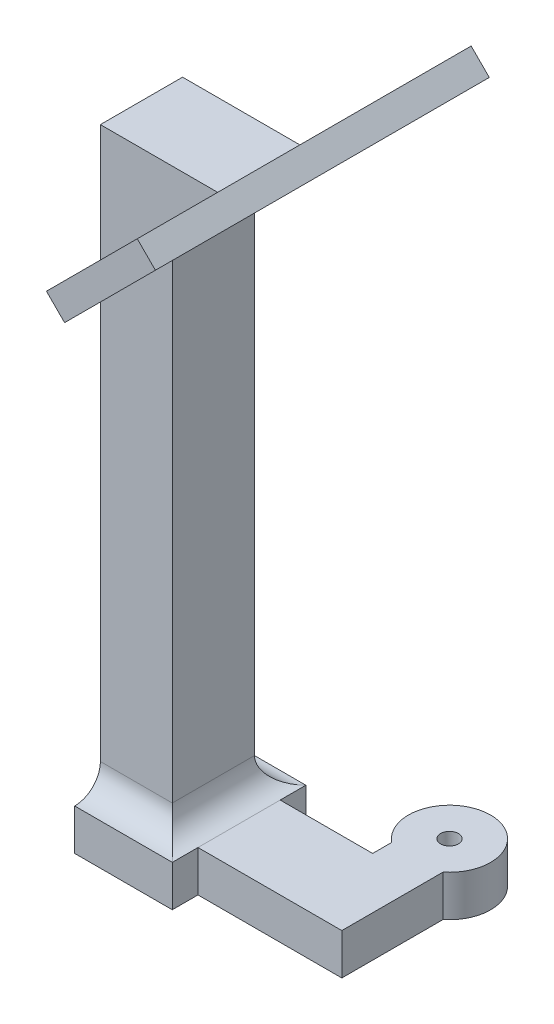
SolidWorks part; units mm, degrees
ref_plane "Front Plane" through (0, 0, 0) normal (0, 0, 1) x (1, 0, 0)
ref_plane "Top Plane" through (0, 0, 0) normal (0, 1, 0) x (1, 0, 0)
ref_plane "Right Plane" through (0, 0, 0) normal (1, 0, 0) x (0, 0, -1)
sketch "Sketch1" plane through (0, 0, 0) normal (1, 0, 0) x (0, 0, -1)
  line L0 (0, 15) -> (80, 15) construction
  line L1 (0, 0) -> (80, 0)
  line L2 (0, 0) -> (0, 30)
  line L3 (0, 30) -> (80, 30)
  line L4 (80, 0) -> (80, 30)
  line L5 (40, 15) -> (40, 30) construction
  circle A0 centre (17.5, 15) radius 1.75
  circle A1 centre (62.5, 15) radius 1.75
  dimension "D3" = 3.5
  dimension "D1" = 80
  dimension "D2" = 30
  dimension "D4" = 45
  dimension "D5" = 22.5
sketch "Sketch3" plane through (0, 0, 0) normal (0, 0, 1) x (1, 0, 0)
  line L0 (-3.5355, 33.5355) -> (0, 30)
  line L1 (0, 30) -> (17.6777, 47.6777)
  line L2 (17.6777, 47.6777) -> (14.1421, 51.2132)
  line L3 (14.1421, 51.2132) -> (-3.5355, 33.5355)
  line L4 (21.6115, 0) -> (-21.6115, 0) construction
  line L5 (0, 15) -> (0, 30) construction
  dimension "D1" = 5
  dimension "D2" = 45
  dimension "D3" = 25
  dimension "D4" = 30
  dimension "D5" = 0
extrude "Boss-Extrude2" add sketch "Sketch3" against normal blind 65
sketch "Sketch4" plane through (-18.5355, 18.5355, 0) normal (-0.7071, 0.7071, 0) x (0, 0, 1)
  line L0 (-65, 33.7132) -> (0, 33.7132) construction
  line L1 (-65, 46.2132) -> (-65, 21.2132) construction
  line L2 (0, 46.2132) -> (0, 21.2132) construction
  line L3 (-32.5, 46.2132) -> (-32.5, 21.2132) construction
  line L4 (-65, 46.2132) -> (0, 46.2132) construction
  line L5 (-65, 21.2132) -> (0, 21.2132) construction
  circle A0 centre (-10, 33.7132) radius 1.75
  circle A1 centre (-55, 33.7132) radius 1.75
  point P16 (-32.5, 33.7132)
  dimension "D3" = 3.5
  dimension "D1" = 45
  dimension "D2" = 22.5
extrude "Cut-Extrude1" cut sketch "Sketch4" against normal through all both and the other way through all
sketch "Sketch5" plane through (-15, 15, 0) normal (0.7071, -0.7071, 0) x (0, 0, -1)
  circle A0 centre (50.4624, 33.7132) radius 2 construction
  circle A1 centre (50.4624, 33.7132) radius 2 construction
sketch "Sketch6" plane through (-18.5355, 18.5355, 0) normal (-0.7071, 0.7071, 0) x (0.7071, 0.7071, 0)
  line L0 (46.2132, 32.5) -> (21.2132, 32.5) construction
  line L1 (46.2132, 65) -> (46.2132, 0) construction
  line L2 (21.2132, 65) -> (21.2132, 0) construction
  point P6 (33.7132, 32.5)
sketch "Sketch8" plane through (0, 0, -65) normal (0, 0, -1) x (-1, 0, 0)
  line L0 (-5.3033, 42.3744) -> (17.5355, 42.3744)
  line L1 (17.5355, 42.3744) -> (17.5355, 30)
  line L2 (17.5355, 30) -> (0, 30)
  line L3 (3.5355, 33.5355) -> (0, 30) construction
  line L4 (-14.1421, 51.2132) -> (3.5355, 33.5355) construction
  line L5 (3.5355, 33.5355) -> (0, 30)
  line L6 (-5.3033, 42.3744) -> (3.5355, 33.5355)
  dimension "D1" = 14
extrude "Boss-Extrude3" add sketch "Sketch8" along normal blind 8 and the other way blind 8 from offset 32.5 contours L1 L2 L5 L6 L0 offset against normal yes
sketch "Sketch9" plane through (0, 30, 0) normal (0, -1, 0) x (1, 0, 0)
  line L1 (-17.5355, -40.5) -> (-3.5355, -40.5)
  line L2 (-17.5355, -40.5) -> (-17.5355, -24.5)
  line L3 (-17.5355, -24.5) -> (-3.5355, -24.5)
  line L4 (-3.5355, -40.5) -> (-3.5355, -24.5)
extrude "Boss-Extrude4" add sketch "Sketch9" along normal blind 100
sketch "Sketch10" plane through (0, -70, 0) normal (0, -1, 0) x (1, 0, 0)
  line L11 (29.4659, -24.5) -> (29.4659, -44.2174)
  line L32 (19.4659, -40.5) -> (19.4659, -44.2174)
  line L42 (29.4659, -24.5) -> (1.4645, -24.5)
  line L43 (1.4645, -40.5) -> (19.4659, -40.5)
  line L45 (-17.5355, -24.5) -> (-17.5355, -40.5)
  line L46 (-17.5355, -40.5) -> (-3.5355, -40.5)
  line L48 (-3.5355, -40.5) -> (-3.5355, -24.5)
  line L52 (-3.5355, -24.5) -> (-17.5355, -24.5)
  line L53 (-17.5355, -24.5) -> (-17.5355, -40.5) construction
  line L54 (-17.5355, -40.5) -> (-3.5355, -40.5) construction
  line L55 (1.4645, -40.5) -> (1.4645, -45.5)
  line L56 (-3.5355, -40.5) -> (-3.5355, -24.5) construction
  line L57 (-3.5355, -24.5) -> (-17.5355, -24.5) construction
  line L58 (-17.5355, -19.5) -> (-17.5355, -45.5)
  line L62 (-22.5355, -19.5) -> (-22.5355, -45.5)
  line L63 (-22.5355, -45.5) -> (1.4645, -45.5)
  line L64 (1.4645, -45.5) -> (1.4645, -19.5)
  line L65 (1.4645, -19.5) -> (-22.5355, -19.5)
  line L67 (-17.5355, -45.5) -> (1.4645, -45.5)
  line L68 (1.4645, -45.5) -> (1.4645, -19.5)
  line L69 (1.4645, -19.5) -> (-17.5355, -19.5)
  circle A0 centre (24.4659, -50.4624) radius 1.75
  arc A2 (19.4659, -44.2174) -> (29.4659, -44.2174) centre (24.4659, -50.4624) ccw
  point P1 (24.4659, -50.4624)
  line M9 (-17.5355, -24.5) -> (-17.5355, -40.5)
  line M10 (-17.5355, -40.5) -> (-3.5355, -40.5)
  line M11 (-3.5355, -40.5) -> (-3.5355, -24.5)
  line M12 (-3.5355, -24.5) -> (-17.5355, -24.5)
  dimension "D3" = 3.5
  dimension "D5" = 3.7174
  dimension "D8" = 16
  dimension "D1" = 5
  dimension "D2" = 0
  dimension "D4" = 5
extrude "Boss-Extrude5" add sketch "Sketch10" along normal blind 8 contours L11 L32 A0 M11 | M12 M9 M10 M11 | M10 M9 M12 | M11 region at (18.3988, -70, -38.0266) region at (1.1424, -70, -32.5) region at (-10.5355, -70, -32.5)
fillet "Fillet4" radius 5 3 edges at (-10.5355, -70, -40.5) (-10.5355, -70, -24.5) (-3.5355, -70, -32.5)
